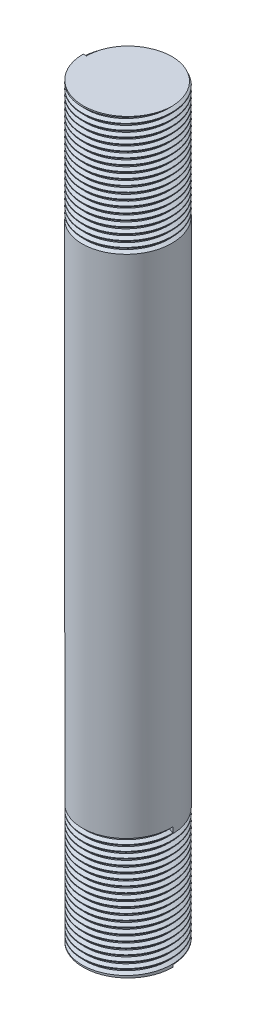
SolidWorks part; units mm, degrees
ref_plane "Alzado" through (0, 0, 0) normal (0, 0, 1) x (1, 0, 0)
ref_plane "Planta" through (0, 0, 0) normal (0, 1, 0) x (1, 0, 0)
ref_plane "Vista lateral" through (0, 0, 0) normal (1, 0, 0) x (0, 0, -1)
sketch "Croquis1" plane through (0, 0, 0) normal (0, 1, 0) x (1, 0, 0)
  circle A0 centre (0, 0) radius 15
  dimension "D1" = 30
extrude "Saliente-Extruir1" add sketch "Croquis1" along normal blind 250
thread "Rosca1" pitch 2 method cut profile "Perfil de rosca2" start angle 0, offset 1, length 40, pitch 2, diameter 30
ref_plane "Plano2" through (-15, 251, 0) normal (0, 0, 1) x (-1, 0, 0)
sketch "Perfil de rosca2" plane through (-15, 251, 0) normal (0, 0, 1) x (-1, 0, 0)
  line L0 (0, 0) -> (0, 2) construction
  line L11 (0, 0) -> (0, 1.75)
  line L12 (0, 1.75) -> (-1.0825, 1.125)
  line L13 (-1.0825, 1.125) -> (-1.0825, 0.625)
  line L15 (-1.0825, 0.625) -> (0, 0)
  line L17 (-1.0825, 0.875) -> (0, 0.875) construction
  point P2 (0, 0)
  dimension "Pitch" = 2
  dimension "Profile_Angle" = 60
  dimension "Profile_Land" = 0.5
  dimension "Profile_Height" = 1.0825
thread "Rosca2" pitch 2 method cut profile "Perfil de rosca3" start angle 0, offset 1, length 40, pitch 2, diameter 30
ref_plane "Plano3" through (15, -1, 0) normal (0, 0, 1) x (1, 0, 0)
sketch "Perfil de rosca3" plane through (15, -1, 0) normal (0, 0, 1) x (1, 0, 0)
  line L0 (0, 0) -> (0, 2) construction
  line L11 (0, 0) -> (0, 1.75)
  line L12 (0, 1.75) -> (-1.0825, 1.125)
  line L13 (-1.0825, 1.125) -> (-1.0825, 0.625)
  line L15 (-1.0825, 0.625) -> (0, 0)
  line L17 (-1.0825, 0.875) -> (0, 0.875) construction
  point P2 (0, 0)
  dimension "Pitch" = 2
  dimension "Profile_Angle" = 60
  dimension "Profile_Land" = 0.5
  dimension "Profile_Height" = 1.0825
